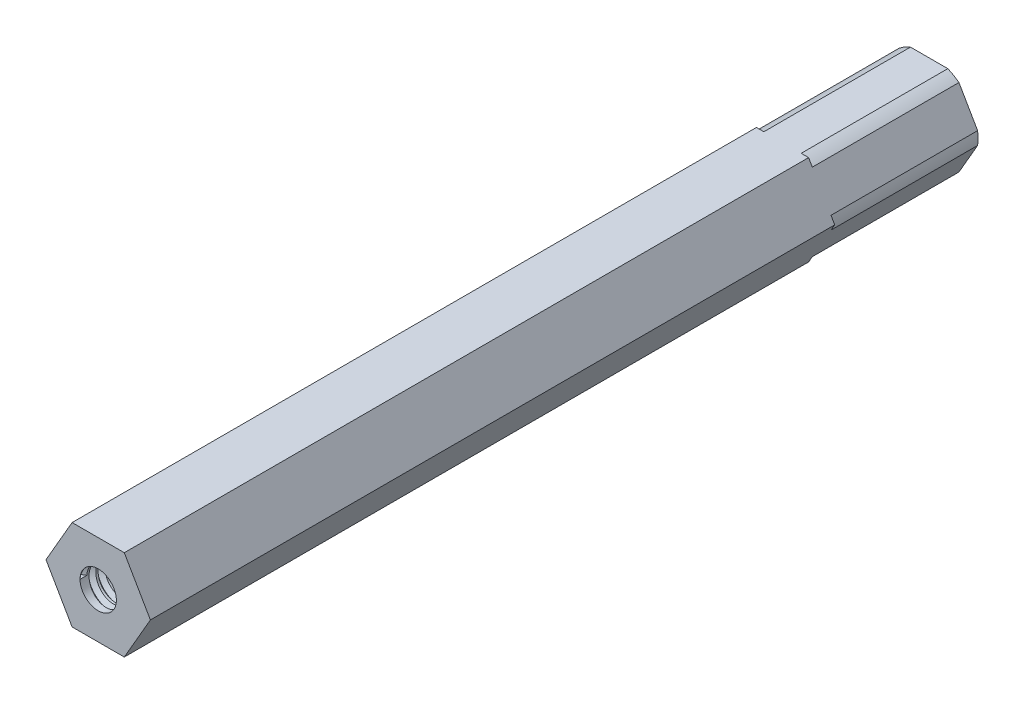
SolidWorks part; units mm, degrees
material "7075-T6 (SN)"
ref_plane "Alzado" through (0, 0, 0) normal (0, 0, 1) x (1, 0, 0)
ref_plane "Planta" through (0, 0, 0) normal (0, 1, 0) x (1, 0, 0)
ref_plane "Vista lateral" through (0, 0, 0) normal (1, 0, 0) x (0, 0, -1)
sketch "Croquis2" plane through (0, 0, 0) normal (0, 0, 1) x (1, 0, 0)
  line L1 (3.6662, -6.35) -> (7.3323, 0)
  line L2 (7.3323, 0) -> (3.6662, 6.35)
  line L3 (3.6662, 6.35) -> (-3.6662, 6.35)
  line L4 (-3.6662, 6.35) -> (-7.3323, 0)
  line L5 (-7.3323, 0) -> (-3.6662, -6.35)
  line L6 (-3.6662, -6.35) -> (3.6662, -6.35)
  circle A0 centre (0, 0) radius 6.35 construction
  dimension "D1" = 12.7
extrude "Extrusión Hex Profile" add sketch "Croquis2" along normal mid plane 116.7384
sketch "Croquis3" plane through (0, 0, 0) normal (0, 0, 1) x (1, 0, 0)
  circle A0 centre (0, 0) radius 2.5527
  dimension "D1" = 5.1054
extrude "Tap Hole 1" cut sketch "Croquis3" against normal blind 19.05 from surface starting at face at (0, 0, 58.3692)
extrude "Tap Hole 2" cut sketch "Croquis3<3>" along normal blind 19.05 from surface starting at face at (0, 0, -58.3692)
sketch "Croquis3<3>" plane through (0, 0, 0) normal (0, 0, 1) x (1, 0, 0) same geometry as "Croquis3"
sketch "Croquis7" plane through (0, 0, 0) normal (0, 0, 1) x (1, 0, 0)
  circle A0 centre (0, 0) radius 6.8707
  dimension "D1" = 13.7414
extrude "ThunderHex" cut sketch "Croquis7" along normal blind 20.5994 from surface flip side to cut starting at face at (2.5527, 0, -58.3692)
sketch "Croquis8" plane through (0, 0, 0) normal (0, 1, 0) x (1, 0, 0)
  line L0 (0, -58.3692) -> (-5.5563, -58.3692) construction
  line L1 (3.6662, -58.3692) -> (-3.6662, -58.3692) construction
  line L3 (0, -58.3692) -> (0, 0) construction
  line L4 (-5.5563, -58.3692) -> (-6.35, -57.5754)
  line L5 (-6.35, -57.5754) -> (-6.35, -56.7817)
  line L6 (-6.35, -56.7817) -> (-5.9055, -56.7817)
  line L7 (-5.9055, -56.7817) -> (-5.9055, -55.1942)
  line L8 (-5.9055, -55.1942) -> (-12.7, -55.1942)
  line L9 (-12.7, -55.1942) -> (-12.7, -58.3692)
  line L10 (-12.7, -58.3692) -> (-5.5563, -58.3692)
  line L11 (-3.6662, -58.3692) -> (-7.3323, -58.3692) construction
  dimension "D1" = 11.811
  dimension "D2" = 12.7
  dimension "D3" = 45
  dimension "D4" = 0.7937
  dimension "D6" = 0.7937
  dimension "D7" = 3.175
  dimension "D8" = 25.4
revolve "Retaining Ring 1" [suppressed] cut sketch "Croquis8" angle 360 about L3
sketch "Croquis9" plane through (0, 0, 0) normal (0, -1, 0) x (1, 0, 0)
  line L0 (0, -58.3692) -> (-5.5563, -58.3692) construction
  line L3 (0, -58.3692) -> (0, 0) construction
  line L4 (-5.5563, -58.3692) -> (-6.35, -57.5754)
  line L5 (-6.35, -57.5754) -> (-6.35, -56.7817)
  line L6 (-6.35, -56.7817) -> (-5.9055, -56.7817)
  line L7 (-5.9055, -56.7817) -> (-5.9055, -55.1942)
  line L8 (-5.9055, -55.1942) -> (-12.7, -55.1942)
  line L9 (-12.7, -55.1942) -> (-12.7, -58.3692)
  line L10 (-12.7, -58.3692) -> (-5.5563, -58.3692)
  line L12 (-2.6237, -58.3692) -> (2.6237, -58.3692) construction
  line L13 (-6.8111, -58.3692) -> (-4.1874, -58.3692) construction
  dimension "D1" = 11.811
  dimension "D2" = 12.7
  dimension "D3" = 45
  dimension "D4" = 0.7937
  dimension "D6" = 0.7937
  dimension "D7" = 3.175
  dimension "D8" = 25.4
revolve "Retaining Ring 2" [suppressed] cut sketch "Croquis9" angle 360 about L3
sketch "Croquis10" plane through (0, 0, 0) normal (0, 1, 0) x (1, 0, 0)
  line L0 (0, -58.3692) -> (0, 0) construction
  line L1 (3.6662, -58.3692) -> (-3.6662, -58.3692) construction
  line L2 (0, -58.3692) -> (-5.5563, -58.3692) construction
  line L3 (-3.6662, -58.3692) -> (-7.3323, -58.3692) construction
  line L4 (-5.5563, -58.3692) -> (-6.35, -57.5755)
  line L5 (-6.35, -57.5755) -> (-6.35, -50.419)
  line L6 (-6.35, -50.419) -> (-9.525, -50.419)
  line L7 (-9.525, -50.419) -> (-9.525, -58.3692)
  line L8 (-9.525, -58.3692) -> (-5.5563, -58.3692)
  dimension "D2" = 12.7
  dimension "D1" = 45
  dimension "D3" = 0.7937
  dimension "D4" = 7.9502
  dimension "D5" = 19.05
revolve "Round End 1" [suppressed] cut sketch "Croquis10" angle 360 about L0
sketch "Croquis12" plane through (0, 0, 0) normal (0, -1, 0) x (1, 0, 0)
  line L0 (0, -58.3692) -> (0, 0) construction
  line L2 (0, -58.3692) -> (-5.5563, -58.3692) construction
  line L4 (-5.5563, -58.3692) -> (-6.35, -57.5755)
  line L5 (-6.35, -57.5755) -> (-6.35, -50.419)
  line L6 (-6.35, -50.419) -> (-9.525, -50.419)
  line L7 (-9.525, -50.419) -> (-9.525, -58.3692)
  line L8 (-9.525, -58.3692) -> (-5.5563, -58.3692)
  line L9 (-2.6237, -58.3692) -> (2.6237, -58.3692) construction
  dimension "D1" = 45
  dimension "D3" = 0.7937
  dimension "D4" = 7.9502
  dimension "D2" = 12.7
  dimension "D5" = 19.05
revolve "Round End 2" [suppressed] cut sketch "Croquis12" angle 360 about L0
thread "Rosca1" pitch 1.27 method cut profile "Perfil de rosca1" start angle 0, offset 0, length 0, pitch 1.27, diameter 5.1054
ref_plane "Plano1" through (-2.5527, 0, 58.3692) normal (0, -1, 0) x (-1, 0, 0)
sketch "Perfil de rosca1" plane through (-2.5527, 0, 58.3692) normal (0, -1, 0) x (-1, 0, 0)
  line L0 (0, 0) -> (0, 1.27) construction
  line L1 (0, 0) -> (0.6874, 0.3969)
  line L2 (0.6874, 0.3969) -> (0.6874, 0.5556)
  line L3 (0.6874, 0.5556) -> (0, 0.9525)
  line L4 (0.6874, 0.4762) -> (0, 0.4762) construction
  line L11 (0, 0) -> (0, 0.9525)
  point P2 (0, 0)
  dimension "Pitch" = 1.27
  dimension "Profile_Angle" = 60
  dimension "Profile_Land" = 0.1588
  dimension "Profile_Height" = 0.6874
thread "Rosca2" pitch 1.27 method cut profile "Perfil de rosca2" start angle 0, offset 0, length 0, pitch 1.27, diameter 5.1054
ref_plane "Plano2" through (2.5527, 0, -58.3692) normal (0, -1, 0) x (1, 0, 0)
sketch "Perfil de rosca2" plane through (2.5527, 0, -58.3692) normal (0, -1, 0) x (1, 0, 0)
  line L0 (0, 0) -> (0, 1.27) construction
  line L1 (0, 0) -> (0.6874, 0.3969)
  line L2 (0.6874, 0.3969) -> (0.6874, 0.5556)
  line L3 (0.6874, 0.5556) -> (0, 0.9525)
  line L4 (0.6874, 0.4762) -> (0, 0.4762) construction
  line L11 (0, 0) -> (0, 0.9525)
  point P2 (0, 0)
  dimension "Pitch" = 1.27
  dimension "Profile_Angle" = 60
  dimension "Profile_Land" = 0.1588
  dimension "Profile_Height" = 0.6874
equation "\"HexOD\"= 0.5pulgadas"
equation "\"Largo\"= 4.596pulgadas"
equation "\"D1@Croquis2\"=\"HexOD\""
equation "\"D1@Extrusión Hex Profile\" = \"Largo\""
equation "\"TapHole\"= IIF ( \"HexOD\" = 0.5pulgadas , 0.2010pulgadas , 0.190pulgadas )"
equation "\"D1@Croquis3\"=\"TapHole\""
equation "\"ProTapHole\"= 0.75pulgadas"
equation "\"D1@Tap Hole 1\" = \"ProTapHole\""
equation "\"D1@Tap Hole 2\" = \"ProTapHole\""
equation "\"ThunderHex\"= IIF ( \"HexOD\" = 0.5pulgadas , 0.541pulgadas , 0.4035pulgadas )"
equation "\"D1@Croquis7\"=\"ThunderHex\""
equation "\"D2@Croquis8\"=\"HexOD\""
equation "\"D1@Croquis8\"=if(\"HexOD\"=0.5pulgadas, 0.465pulgadas, 0.35pulgadas )"
equation "\"D2@Croquis9\"=\"HexOD\""
equation "\"D1@Croquis9\"=if(\"HexOD\"=0.5pulgadas, 0.465pulgadas, 0.35pulgadas )"
equation "\"D8@Croquis8\"=\"HexOD\"*2"
equation "\"D8@Croquis9\"=\"HexOD\"*2"
equation "\"D5@Croquis10\"=\"HexOD\"*1.5"
equation "\"D5@Croquis12\"=\"HexOD\"*1.5"
equation "\"D4@Croquis10\"=if( \"D2@Croquis10\"=<0.375, 0.28, 0.313)"
equation "\"D4@Croquis12\"=if( \"D2@Croquis10\"=<0.375, 0.28, 0.313)"
